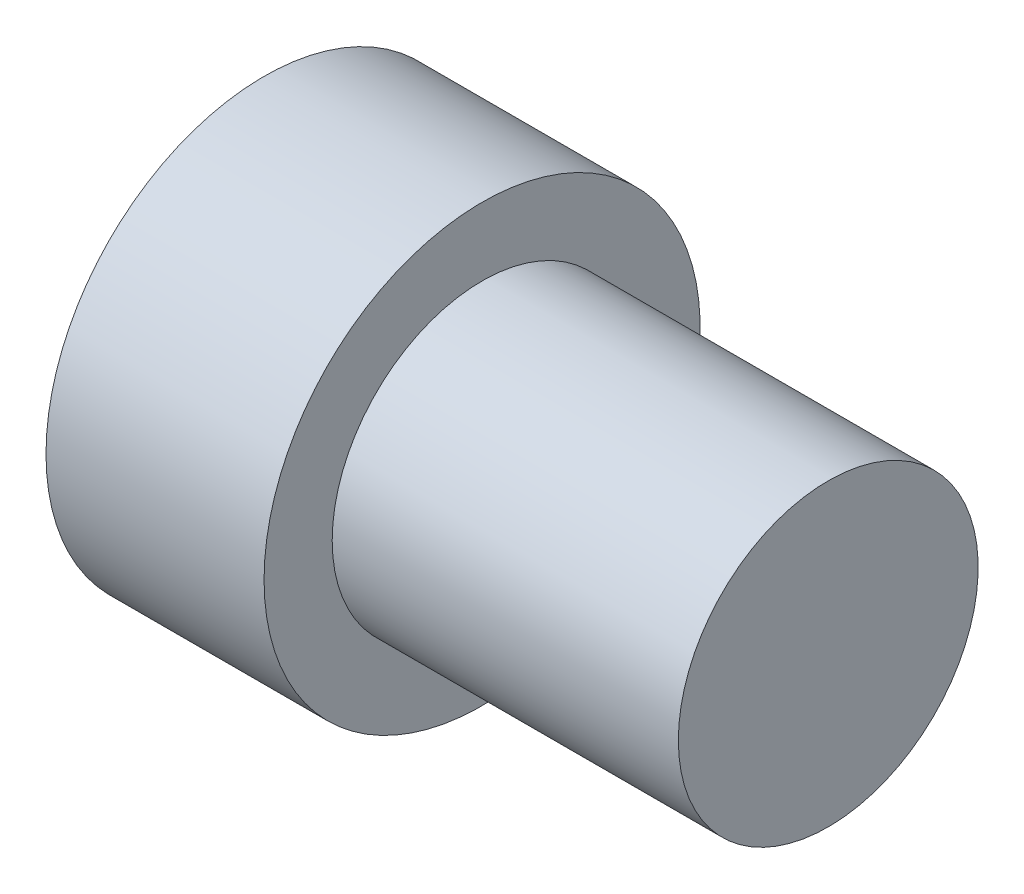
SolidWorks part; units mm, degrees
ref_plane "Front Plane" through (0, 0, 0) normal (0, 0, 1) x (1, 0, 0)
ref_plane "Top Plane" through (0, 0, 0) normal (0, 1, 0) x (1, 0, 0)
ref_plane "Right Plane" through (0, 0, 0) normal (1, 0, 0) x (0, 0, -1)
sketch "Burst_Disc Sketch" plane through (0, 0, 0) normal (0, 0, 1) x (1, 0, 0)
  line L0 (-1000, 0) -> (1000, 0) construction
  line L1 (12.7, 0) -> (12.7, 5.5)
  line L2 (12.7, 5.5) -> (0, 5.5)
  line L3 (0, 5.5) -> (0, 8)
  line L4 (0, 8) -> (-8, 8)
  line L5 (-8, 8) -> (-8, 0)
  line L6 (-8, 0) -> (12.7, 0)
revolve "Burst_Disc" add sketch "Burst_Disc Sketch" angle 360 about L0
ref_axis "Engine Axis" through (13.735, 0, 0) along (-1, 0, 0)
